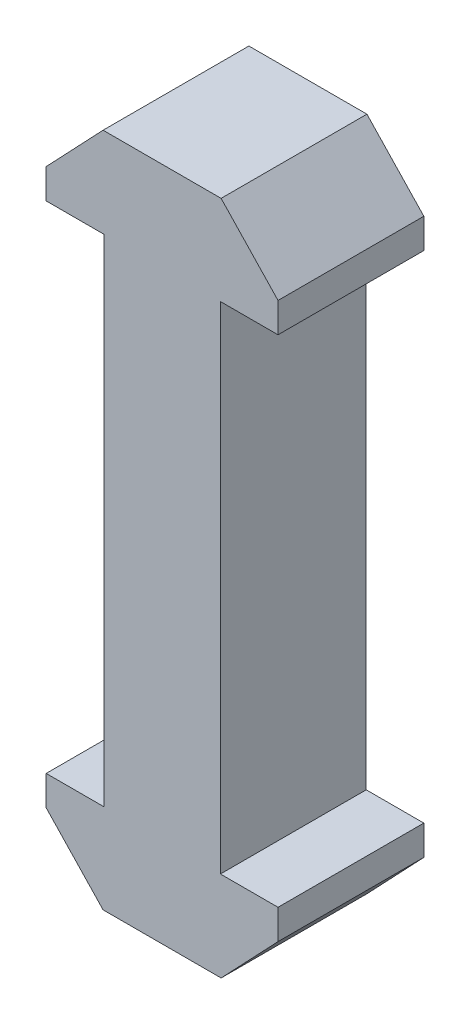
SolidWorks part; units mm, degrees
ref_plane "Front Plane" through (0, 0, 0) normal (0, 0, 1) x (1, 0, 0)
ref_plane "Top Plane" through (0, 0, 0) normal (0, 1, 0) x (1, 0, 0)
ref_plane "Right Plane" through (0, 0, 0) normal (1, 0, 0) x (0, 0, -1)
sketch "Sketch1" plane through (0, 0, 0) normal (0, 0, 1) x (1, 0, 0)
  line L3 (0, 0) -> (0, 14.8775) construction
  line L8 (0, 14.8775) -> (-8.6643, 14.8775) construction
  line L14 (4, 31.8775) -> (4, -2.1225)
  line L15 (-4, 31.8775) -> (-4, -2.1225)
  line B0 (7.95, -2.1225) -> (7.95, -4.1625)
  line B1 (4.048, -8.2749) -> (-4.048, -8.2749)
  line B2 (-7.95, -4.1625) -> (-7.95, -2.1225)
  line B3 (-7.95, -2.1225) -> (7.95, -2.1225)
  line B4 (7.95, -4.1625) -> (4.048, -8.2749)
  line B5 (-4.048, -8.2749) -> (-7.95, -4.1625)
  line B6 (7.95, 31.8775) -> (7.95, 33.9175)
  line B7 (4.048, 38.0299) -> (-4.048, 38.0299)
  line B8 (-7.95, 33.9175) -> (-7.95, 31.8775)
  line B9 (-7.95, 31.8775) -> (7.95, 31.8775)
  line B10 (7.95, 33.9175) -> (4.048, 38.0299)
  line B11 (-4.048, 38.0299) -> (-7.95, 33.9175)
  dimension "D1" = 34
  dimension "D5" = 8
sketch_block_instance "Block1-1"
sketch_block "Block1" parameters "D1"=8.44, "D2"=2.6, "D3"=6, "D4"=16.7, "D6"=5.6686, "D7"=2.0404, "D8"=8.0963, "D9"=15.9, "D5"=2.4157
sketch_block_instance "Block1-5"
extrude "Boss-Extrude1" add sketch "Sketch1" along normal mid plane 10 contours B0 | L15 B0 L14 | B11 B8 B9 B6 B10 B7 region at (0, 14.8775, 0) region at (0, 34.6191, 0) region at (0, -4.864, 0)
equation "\"SmallJarHeight\"=65"
